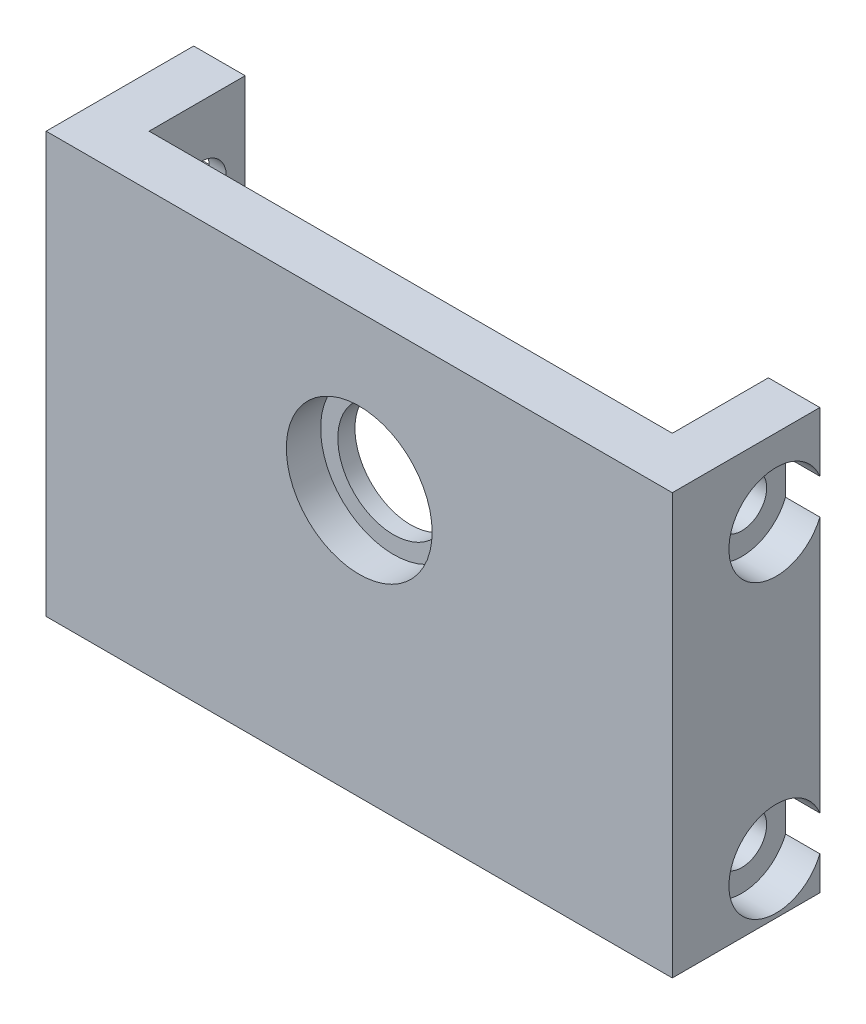
SolidWorks part; units mm, degrees
ref_plane "Plano frontal" through (0, 0, 0) normal (0, 0, 1) x (1, 0, 0)
ref_plane "Plano superior" through (0, 0, 0) normal (0, 1, 0) x (1, 0, 0)
ref_plane "Plano direito" through (0, 0, 0) normal (1, 0, 0) x (0, 0, -1)
sketch "Esboço2" plane through (0, 0, 0) normal (0, 0, 1) x (1, 0, 0)
  line L0 (2.5, -18.5) -> (4.5, -18.5) construction
  line L1 (-0.25, 3) -> (30.25, 3)
  line L2 (-0.25, 3) -> (-0.25, -21.5)
  line L3 (-0.25, -21.5) -> (30.25, -21.5)
  line L4 (30.25, 3) -> (30.25, -21.5)
  line L7 (0, -38.6) -> (0, 0) construction
  line L9 (-0.25, -1.1531) -> (0, -1.1531) construction
  line L11 (30, -1.6003) -> (30.25, -1.6003) construction
  line L12 (30, -38.6) -> (30, 0) construction
  arc A0 (18.9245, -1.4615) -> (9.4709, -3.67) centre (15, -6) ccw construction
  dimension "D1" = 9
  dimension "D2" = 0.25
  dimension "D3" = 3
extrude "Ressalto-extrusão1" add sketch "Esboço2" along normal blind 3 from offset 0.25
ref_plane "Plano1" through (15, 0, 0) normal (-1, 0, 0) x (0, 0, 1)
sketch "Esboço3" plane through (-0.25, 0, 0) normal (-1, 0, 0) x (0, 0, 1)
  line L0 (3.25, -21.5) -> (0.25, -21.5) construction
  line L1 (3.25, 3) -> (-5.35, 3)
  line L2 (3.25, 3) -> (3.25, -21.5)
  line L3 (3.25, -21.5) -> (-5.35, -21.5)
  line L4 (-5.35, 3) -> (-5.35, -21.5)
  dimension "D1" = 0.25
extrude "Ressalto-extrusão2" add sketch "Esboço3" along normal blind 3
mirror "Espelhar1" about plane through (15, 0, 0) normal (-1, 0, 0) of "Ressalto-extrusão2"
sketch "Esboço5" plane through (0, 0, 3.25) normal (0, 0, 1) x (1, 0, 0)
  circle A2 centre (15, -6) radius 4.25
  circle A3 centre (15, -6) radius 4 construction
  dimension "D1" = 0.25
extrude "Corte-extrusão1" cut sketch "Esboço5" against normal offset from surface (2 mm away) 1 up to face at (15, -9.25, 0.25)
sketch "Esboço12" plane through (0, 0, 1.25) normal (0, 0, 1) x (1, 0, 0)
  circle A0 centre (15, -6) radius 3.25 construction
  circle A1 centre (15, -6) radius 3.25
extrude "Corte-extrusão3" cut sketch "Esboço12" against normal through all
ref_plane "Plane1" through (15, 0, 0) normal (-1, 0, 0) x (0, 0, 1)
hole_wizard "CBORE for M2.5 SHCS1" positions "Sketch3" profile "Sketch4" counterbore size "M2.5" standard "ANSI Metric" end condition up to next
sketch "Sketch3" plane through (-3.25, 0, 0) normal (-1, 0, 0) x (0, 0, 1)
  circle A0 centre (-2.8, -1.5) radius 1.35 construction
  circle A1 centre (-2.8, -18.5) radius 1.35 construction
  point P0 (-2.8, -1.5)
  point P2 (-2.8, -18.5)
sketch "Sketch4" plane through (-3.25, -1.5, -2.8) normal (0, 1, 0) x (0, 0, 1)
  line L0 (0, 0) -> (0, 3)
  line L1 (0, 3) -> (1.45, 3)
  line L3 (1.45, 3) -> (1.45, 2)
  line L4 (1.45, 2) -> (2.75, 2)
  line L5 (2.75, 2) -> (2.75, 0)
  line L7 (2.75, 0) -> (0, 0)
  line L11 (0, -6.35) -> (0, 107.95) construction
  dimension "Thru Hole Dia." = 2.9
  dimension "Thru Hole Depth" = 3
  dimension "C'Bore Dia." = 5.5
  dimension "C'Bore Depth" = 2
mirror "Mirror1" about plane through (15, 0, 0) normal (-1, 0, 0) of "CBORE for M2.5 SHCS1"
